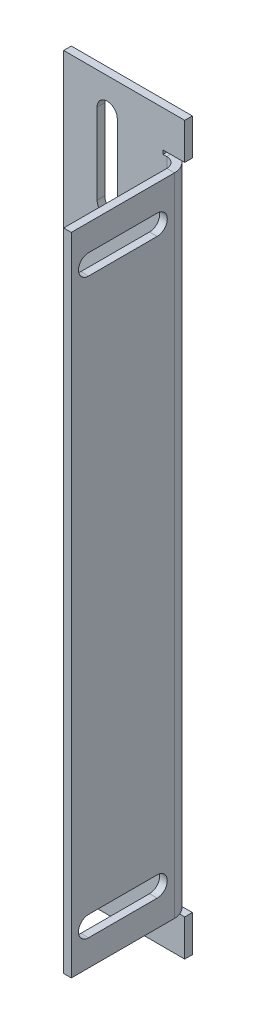
SolidWorks part; units mm, degrees
note: The reader was unsure of these and kept them because the rebuilt part matched: flange length of "Edge-Flange1".
ref_plane "Front Plane" through (0, 0, 0) normal (0, 0, 1) x (1, 0, 0)
ref_plane "Top Plane" through (0, 0, 0) normal (0, 1, 0) x (1, 0, 0)
ref_plane "Right Plane" through (0, 0, 0) normal (1, 0, 0) x (0, 0, -1)
sketch "Sketch1" plane through (0, 0, 0) normal (0, 0, 1) x (1, 0, 0)
  line L1 (-30, 66.8554) -> (0, 66.8554)
  line L2 (-30, 66.8554) -> (-30, -113.1446)
  line L3 (-30, -113.1446) -> (0, -113.1446)
  line L4 (0, 66.8554) -> (0, -113.1446)
  dimension "D1" = 180
  dimension "D2" = 30
base flange "Base-Flange1" sketch "Sketch1" thickness 1.8974 reverse thickness direction no parameters "D1"=2.54
edge flange "Edge-Flange1" sketch "Sketch8" flange angle 90 flange length 30 flange position material inside bend radius 2.54 thickness 1.8974 relief rectangular parameters "D6"=10
sketch "Sketch8" plane through (0, 0, 0) normal (1, 0, 0) x (0, 1, 0)
  line L0 (-113.1446, 0) -> (66.8554, 0) construction
  line L1 (-103.1446, 0) -> (56.8554, 0)
  line L2 (-103.1446, 0) -> (-103.1446, 28.1026)
  line L3 (-103.1446, 28.1026) -> (56.8554, 28.1026)
  line L4 (56.8554, 28.1026) -> (56.8554, 0)
  dimension "D1" = 10
  dimension "D2" = 10
bend "EdgeBend1" bend radius 2.54 bend angle 90 parameters "D5"=1
sketch "Sketch9" plane through (-1.8974, 0, 0) normal (-1, 0, 0) x (0, 0, 1)
  line L0 (28.1026, 56.8554) -> (28.1026, -103.1446) construction
  line L1 (23.8213, 47.8554) -> (6.8213, 47.8554) construction
  line L2 (23.8213, 45.3554) -> (6.8213, 45.3554)
  line L3 (23.8213, 50.3554) -> (6.8213, 50.3554)
  line L4 (2.54, 56.8554) -> (28.1026, 56.8554) construction
  line L5 (28.1026, -103.1446) -> (2.54, -103.1446) construction
  line L6 (6.8213, -94.1446) -> (23.8213, -94.1446) construction
  line L7 (6.8213, -91.6446) -> (23.8213, -91.6446)
  line L8 (6.8213, -96.6446) -> (23.8213, -96.6446)
  arc A0 (23.8213, 45.3554) -> (23.8213, 50.3554) centre (23.8213, 47.8554) ccw
  arc A1 (6.8213, 50.3554) -> (6.8213, 45.3554) centre (6.8213, 47.8554) ccw
  arc A2 (6.8213, -91.6446) -> (6.8213, -96.6446) centre (6.8213, -94.1446) ccw
  arc A3 (23.8213, -96.6446) -> (23.8213, -91.6446) centre (23.8213, -94.1446) ccw
  point P0 (28.1026, -23.1446)
  point P1 (28.1026, 47.8554)
  point P4 (28.1026, -94.1446)
  point P7 (15.3213, 47.8554)
  point P12 (15.3213, 56.8554)
  point P13 (15.3213, -103.1446)
  point P20 (15.3213, -94.1446)
  dimension "D1" = 71
  dimension "D2" = 71
extrude "Cut-Extrude1" cut sketch "Sketch9" against normal blind 10 normal cut yes
sketch "Sketch10" plane through (0, 0, 0) normal (1, 0, 0) x (0, 0, -1)
  line L0 (-28.1026, 56.8554) -> (-28.1026, -103.1446) construction
  point P0 (-28.1026, -23.1446)
sketch "Sketch11" plane through (0, 0, -1.8974) normal (0, 0, -1) x (-1, 0, 0)
  line L0 (19.209, -105.1446) -> (19.209, -85.1446) construction
  line L1 (16.709, -105.1446) -> (16.709, -85.1446)
  line L2 (21.709, -105.1446) -> (21.709, -85.1446)
  line L3 (19.209, 38.8554) -> (19.209, 58.8554) construction
  line L4 (16.709, 38.8554) -> (16.709, 58.8554)
  line L5 (21.709, 38.8554) -> (21.709, 58.8554)
  line L6 (30, -113.1446) -> (0, -113.1446) construction
  line L7 (0, 66.8554) -> (30, 66.8554) construction
  arc A0 (16.709, -105.1446) -> (21.709, -105.1446) centre (19.209, -105.1446) ccw
  arc A1 (21.709, -85.1446) -> (16.709, -85.1446) centre (19.209, -85.1446) ccw
  arc A2 (16.709, 38.8554) -> (21.709, 38.8554) centre (19.209, 38.8554) ccw
  arc A3 (21.709, 58.8554) -> (16.709, 58.8554) centre (19.209, 58.8554) ccw
  point P3 (19.209, -95.1446)
  point P8 (19.209, 48.8554)
  dimension "D1" = 8
  dimension "D2" = 8
extrude "Cut-Extrude2" cut sketch "Sketch11" against normal blind 10 normal cut yes
sketch "Bend-Lines1" [suppressed] plane through (0, 0, 0) normal (0, 1, 0) x (1, 0, 0)
sketch "Bounding-Box1" [suppressed] plane through (0, 0, 0) normal (0, 1, 0) x (1, 0, 0)
sheet metal parameters "Sheet-Metal1" thickness 1.8974 parameters "D1"=2.54
flat pattern "Flat-Pattern1" [suppressed]
sketch "Bend-Lines2" plane through (0, 0, 0) normal (0, 1, 0) x (1, 0, 0)
sketch "Bounding-Box2" [suppressed] plane through (0, 0, 0) normal (0, 1, 0) x (1, 0, 0)
sheet metal parameters "Sheet-Metal2" thickness 1.8974 parameters "D1"=2.54
flat pattern "Flat-Pattern1" [suppressed]
sketch "Bend-Lines2" plane through (0, 0, 0) normal (0, 1, 0) x (1, 0, 0)
sketch "Bounding-Box2" [suppressed] plane through (0, 0, 0) normal (0, 1, 0) x (1, 0, 0)
bend of the flat pattern "Flatten-<EdgeBend1>1"
sheet metal parameters "Sheet-Metal3" thickness 1.8974 parameters "D1"=2.54
flat pattern "Flat-Pattern1" [suppressed]
sketch "Bend-Lines2" plane through (0, 0, 0) normal (0, 1, 0) x (1, 0, 0)
sketch "Bounding-Box2" [suppressed] plane through (0, 0, 0) normal (0, 1, 0) x (1, 0, 0)
bend of the flat pattern "Flatten-<EdgeBend1>1"
sheet metal parameters "Sheet-Metal4" thickness 1.8974 parameters "D1"=2.54
flat pattern "Flat-Pattern1" [suppressed]
sketch "Bend-Lines2" plane through (0, 0, 0) normal (0, 0, 1) x (1, 0, 0)
  line L0 (-1.6974, -103.1446) -> (-1.6974, 56.8554) construction
  line L1 (-1.6974, -103.1446) -> (-1.6974, 56.8554) construction
sketch3d "Bounding-Box2" [suppressed]
  line L0 (26.6053, 66.8554, 0) -> (26.6053, -113.1446, 0) construction
  line L1 (-30, 66.8554, 0) -> (-30, -113.1446, 0) construction
  line L2 (26.6053, 66.8554, 0) -> (-30, 66.8554, 0) construction
  line L3 (26.6053, -113.1446, 0) -> (-30, -113.1446, 0) construction
bend of the flat pattern "Flatten-<EdgeBend1>1"
sketch "Sketch10-1" [suppressed] plane through (-1.4974, 0, -1.8974) normal (0, 0, -1) x (-1, 0, 0)
  point P0 (-28.1026, -23.1446)
